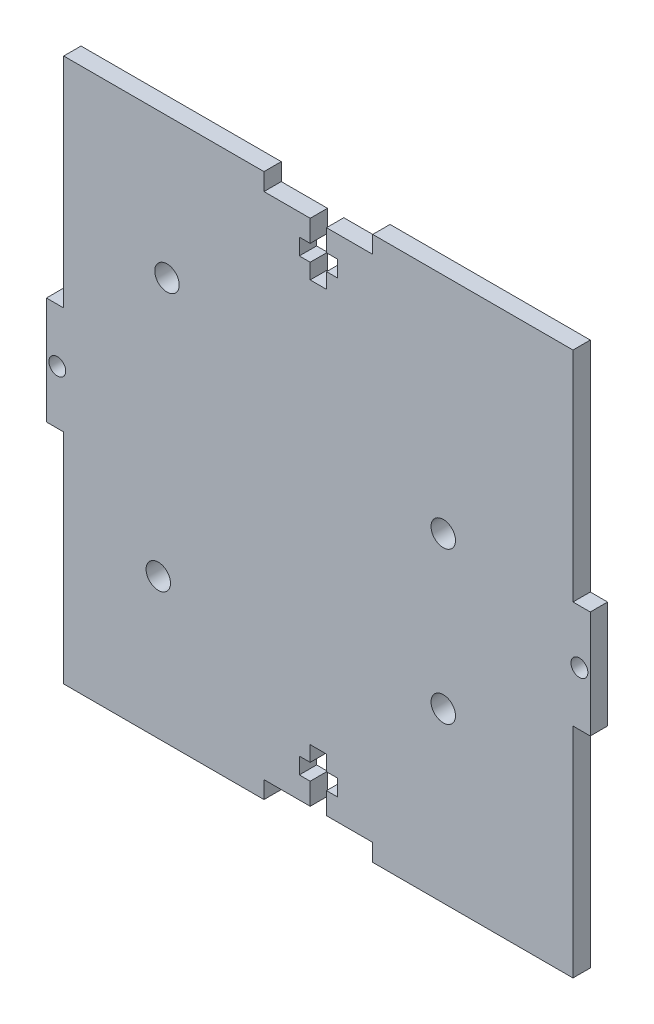
SolidWorks part; units mm, degrees
ref_plane "Front Plane" through (0, 0, 0) normal (0, 0, 1) x (1, 0, 0)
ref_plane "Top Plane" through (0, 0, 0) normal (0, 1, 0) x (1, 0, 0)
ref_plane "Right Plane" through (0, 0, 0) normal (1, 0, 0) x (0, 0, -1)
sketch "Sketch1" plane through (0, 0, 0) normal (0, 0, 1) x (1, 0, 0)
  line L0 (0, 40) -> (0, -40) construction
  line L5 (-50, -50) -> (50, 50) construction
  line L6 (-50, 50) -> (50, -50) construction
  line L7 (-100, 0) -> (100, 0) construction
  line L32 (-50, 50) -> (50, 50)
  line L35 (50, 50) -> (50, -50)
  line L36 (50, -50) -> (-50, -50)
  line L37 (-50, -50) -> (-50, 50)
  point P0 (0, 0)
  dimension "D1" = 100
  dimension "D2" = 100
extrude "Boss-Extrude2" add sketch "Sketch1" along normal blind 3.18
sketch "Sketch2" plane through (0, 0, 3.18) normal (0, 0, 1) x (1, 0, 0)
  line L0 (0, -50) -> (0, 50) construction
  line L1 (-123.0225, 0) -> (147.0753, 0) construction
  line L2 (50, 50) -> (-50, 50) construction
  line L4 (-10, 50) -> (-10, 46.82)
  line L5 (-10, 46.82) -> (-1.5, 46.82)
  line L6 (10, 50) -> (10, 46.82)
  line L7 (1.5, 46.82) -> (10, 46.82)
  line L9 (-1.5, 46.82) -> (-1.5, 42.82)
  line L10 (-1.5, 37) -> (1.5, 37)
  line L11 (1.5, 46.82) -> (1.5, 42.82)
  line L12 (-3.5, 42.82) -> (-1.5, 42.82)
  line L13 (-3.5, 42.82) -> (-3.5, 39.82)
  line L14 (-3.5, 39.82) -> (-1.5, 39.82)
  line L15 (3.5, 42.82) -> (3.5, 39.82)
  line L16 (1.5, 42.82) -> (3.5, 42.82)
  line L17 (-1.5, 39.82) -> (-1.5, 37)
  line L18 (1.5, 39.82) -> (1.5, 37)
  line L19 (1.5, 39.82) -> (3.5, 39.82)
  line L20 (-10, 50) -> (10, 50)
  line L21 (-50, -50) -> (50, -50) construction
  line L22 (-50, 50) -> (-50, -50) construction
  line L23 (-50, 9.875) -> (-46.82, 9.875)
  line L24 (-50, 9.875) -> (-50, 50)
  line L25 (-50, 50) -> (-46.82, 50)
  line L26 (-46.82, 9.875) -> (-46.82, 50)
  line L28 (-50, -9.875) -> (-46.82, -9.875)
  line L29 (-50, -9.875) -> (-50, -50)
  line L30 (-50, -50) -> (-46.82, -50)
  line L31 (-46.82, -9.875) -> (-46.82, -50)
  circle A0 centre (-48, 0) radius 1.55
  dimension "D11" = 3.1
  dimension "D12" = 2
  dimension "D1" = 4
  dimension "D2" = 3
  dimension "D3" = 3
  dimension "D4" = 20
  dimension "D5" = 7
  dimension "D6" = 3.18
  dimension "D7" = 13
  dimension "D8" = 19.75
  dimension "D9" = 3.18
  dimension "D10" = 3.18
extrude "Cut-Extrude1" cut sketch "Sketch2" against normal through all
mirror "Mirror1" about plane through (0, 0, 0) normal (0, 1, 0) of "Cut-Extrude1"
mirror "Mirror3" about plane through (0, 0, 0) normal (1, 0, 0) of "Cut-Extrude1"
sketch "Sketch3" plane through (0, 0, 0) normal (0, 0, -1) x (-1, 0, 0)
  circle A0 centre (27.8324, 24.15) radius 2.25
  circle A1 centre (29.4324, -24.15) radius 2.25
  circle A2 centre (-22.9676, -19.05) radius 2.25
  circle A3 centre (-22.9676, 8.85) radius 2.25
  dimension "D1" = 4.5
  dimension "D2" = 4.5
  dimension "D3" = 4.5
  dimension "D4" = 4.5
extrude "Cut-Extrude2" cut sketch "Sketch3" against normal through all
